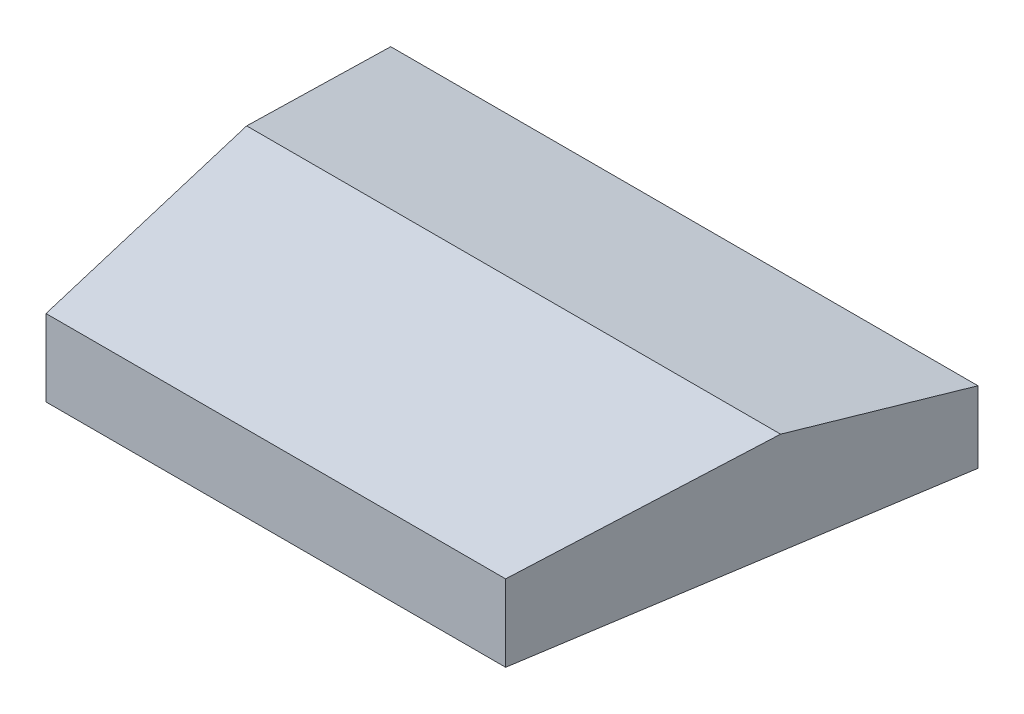
SolidWorks part; units mm, degrees
ref_plane "Front Plane" through (0, 0, 0) normal (0, 0, 1) x (1, 0, 0)
ref_plane "Top Plane" through (0, 0, 0) normal (0, 1, 0) x (1, 0, 0)
ref_plane "Right Plane" through (0, 0, 0) normal (1, 0, 0) x (0, 0, -1)
sketch "Sketch1" plane through (0, 0, 0) normal (0, 1, 0) x (1, 0, 0)
  line L1 (0, 0) -> (292.1, 0)
  line L5 (0, 0) -> (292.1, 0) construction
  line L6 (0, 0) -> (292.1, 0) construction
  line L7 (31.75, -203.2) -> (260.35, -203.2)
  line L9 (0, 0) -> (31.75, -203.2)
  line L10 (292.1, 0) -> (260.35, -203.2)
  point P2 (0, 0)
  point P4 (0, 0)
  dimension "D1" = 292.1
  dimension "D2" = 203.2
  dimension "D3" = 228.6
extrude "Boss-Extrude1" add sketch "Sketch1" along normal blind 50.8 contours L1 L10 L7 L9
chamfer "Chamfer1" distance 12.7 angle 84 1 edges at (146.05, 50.8, 203.2) first distance on face at (146.05, 25.4, 203.2)
chamfer "Chamfer2" distance 15.24 angle 80 1 edges at (146.05, 50.8, 0) first distance on face at (146.05, 25.4, 0)
